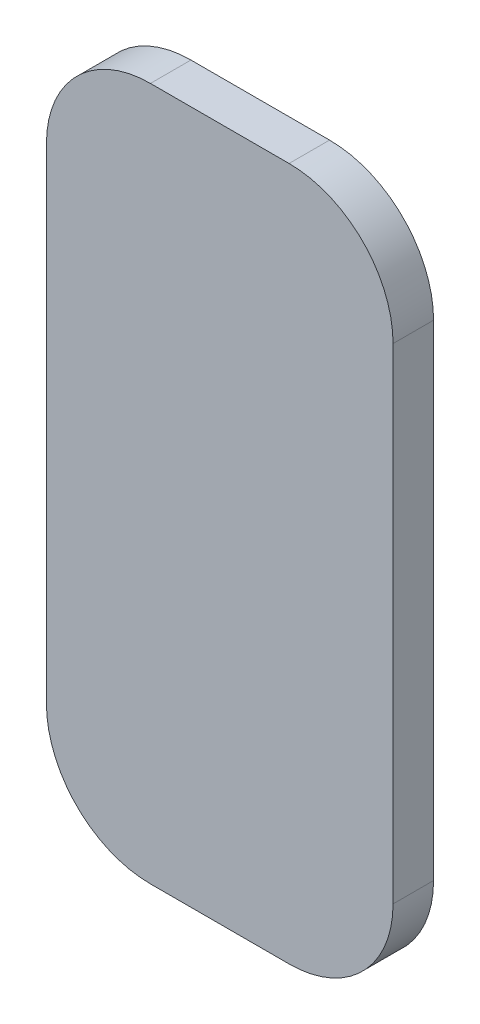
SolidWorks part; units mm, degrees
note: The reader was unsure of these and kept them because the rebuilt part matched: thickness of "Base-Flange1", "Sheet-Metal1".
ref_plane "Front Plane" through (0, 0, 0) normal (0, 0, 1) x (1, 0, 0)
ref_plane "Top Plane" through (0, 0, 0) normal (0, 1, 0) x (1, 0, 0)
ref_plane "Right Plane" through (0, 0, 0) normal (1, 0, 0) x (0, 0, -1)
sketch "Sketch1" plane through (0, 0, 0) normal (0, 0, 1) x (1, 0, 0)
  line L1 (0, 0) -> (10, 0)
  line L2 (0, 0) -> (0, 20)
  line L3 (0, 20) -> (10, 20)
  line L4 (10, 0) -> (10, 20)
  dimension "D1" = 10
  dimension "D2" = 20
base flange "Base-Flange1" sketch "Sketch1" thickness 1.1684 reverse thickness direction no parameters "D1"=1.75
fillet "Fillet1" radius 3 4 edges at (0, 20, -0.5842) (0, 0, -0.5842) (10, 0, -0.5842) (10, 20, -0.5842)
sketch "Bend-Lines1" [suppressed] plane through (0, 0, 0) normal (0, 1, 0) x (1, 0, 0)
sketch "Bounding-Box1" [suppressed] plane through (0, 0, 0) normal (0, 1, 0) x (1, 0, 0)
sheet metal parameters "Sheet-Metal1" thickness 1.1684 parameters "D1"=1.75, "D7"=1.016
flat pattern "Flat-Pattern1" [suppressed]
sketch "Bend-Lines2" plane through (0, 0, 0) normal (0, 1, 0) x (1, 0, 0)
sketch3d "Bounding-Box2" [suppressed]
  line L0 (10, 0, 0) -> (10, 20, 0) construction
  line L1 (0, 0, 0) -> (0, 20, 0) construction
  line L2 (10, 0, 0) -> (0, 0, 0) construction
  line L3 (10, 20, 0) -> (0, 20, 0) construction
